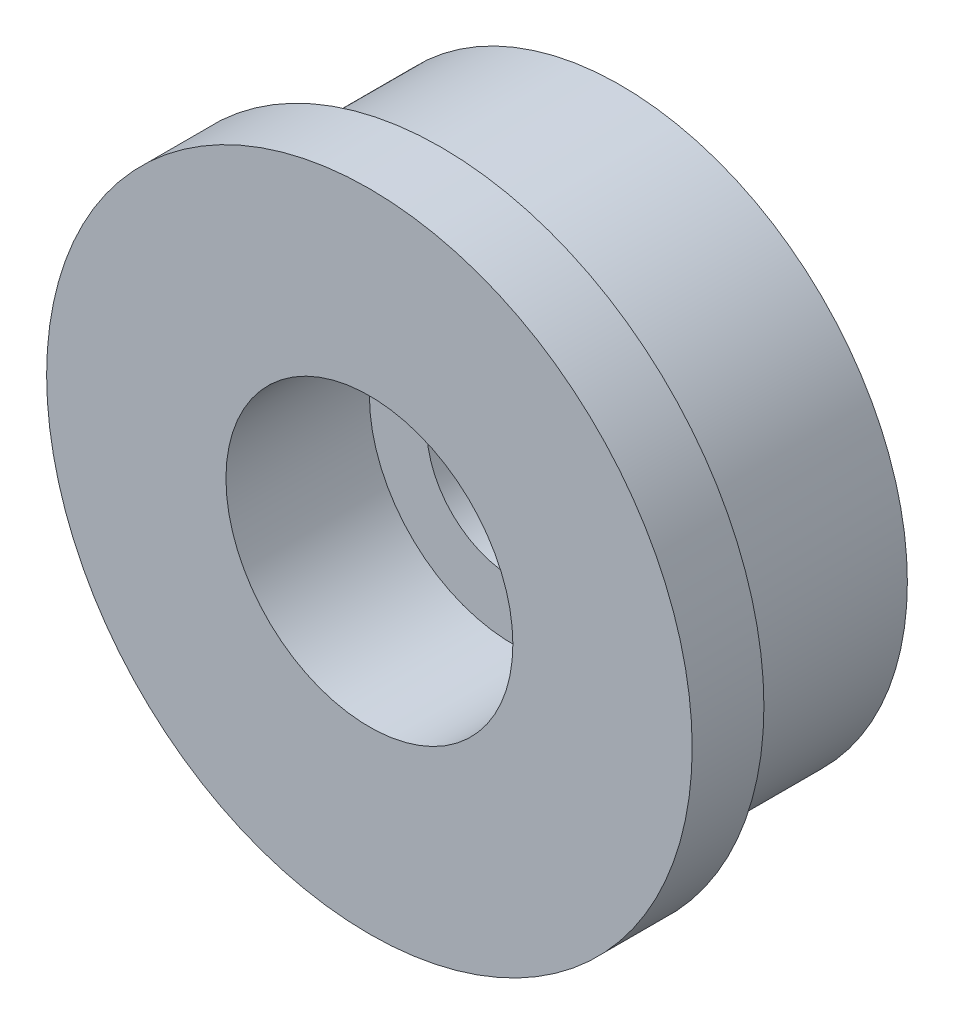
SolidWorks part; units mm, degrees
ref_plane "前视基准面" through (0, 0, 0) normal (0, 0, 1) x (1, 0, 0)
ref_plane "上视基准面" through (0, 0, 0) normal (0, 1, 0) x (1, 0, 0)
ref_plane "右视基准面" through (0, 0, 0) normal (1, 0, 0) x (0, 0, -1)
sketch "草图1" plane through (0, 0, 0) normal (0, 0, 1) x (1, 0, 0)
  circle A0 centre (0, 0) radius 9
extrude "凸台-拉伸1" add sketch "草图1" along normal blind 2
sketch "草图2" plane through (0, 0, 0) normal (0, 0, 1) x (1, 0, 0)
  circle A0 centre (0, 0) radius 8
extrude "凸台-拉伸2" add sketch "草图2" against normal blind 5
hole_wizard "M4 六角凹头盖的柱孔2" positions "3D草图1" profile "草图4" counterbore size "M4" standard "BSI" end condition through all
sketch3d "3D草图1"
  point P5 (0, 0, 2)
  point P8 (0, 0, 0)
sketch "草图4" plane through (0, 0, 2) normal (1, 0, 0) x (0, -1, 0)
  line L0 (0, 0) -> (0, 7)
  line L1 (0, 7) -> (2.4, 7)
  line L3 (2.4, 7) -> (2.4, 4)
  line L4 (2.4, 4) -> (4, 4)
  line L5 (4, 4) -> (4, 0)
  line L7 (4, 0) -> (0, 0)
  line L11 (0, -6.35) -> (0, 107.95) construction
  dimension "通孔孔直径" = 4.8
  dimension "通孔孔深度" = 7
  dimension "柱形沉头孔直径" = 8
  dimension "柱形沉头孔深度" = 4
ref_plane "基准面1" through (0, 0, -5) normal (0, 0, -1) x (-1, 0, 0)
sketch "草图5" plane through (0, 0, -5) normal (0, 0, -1) x (-1, 0, 0)
  circle A0 centre (0, 0) radius 4
extrude "切除-拉伸3" cut sketch "草图5" against normal blind 2
